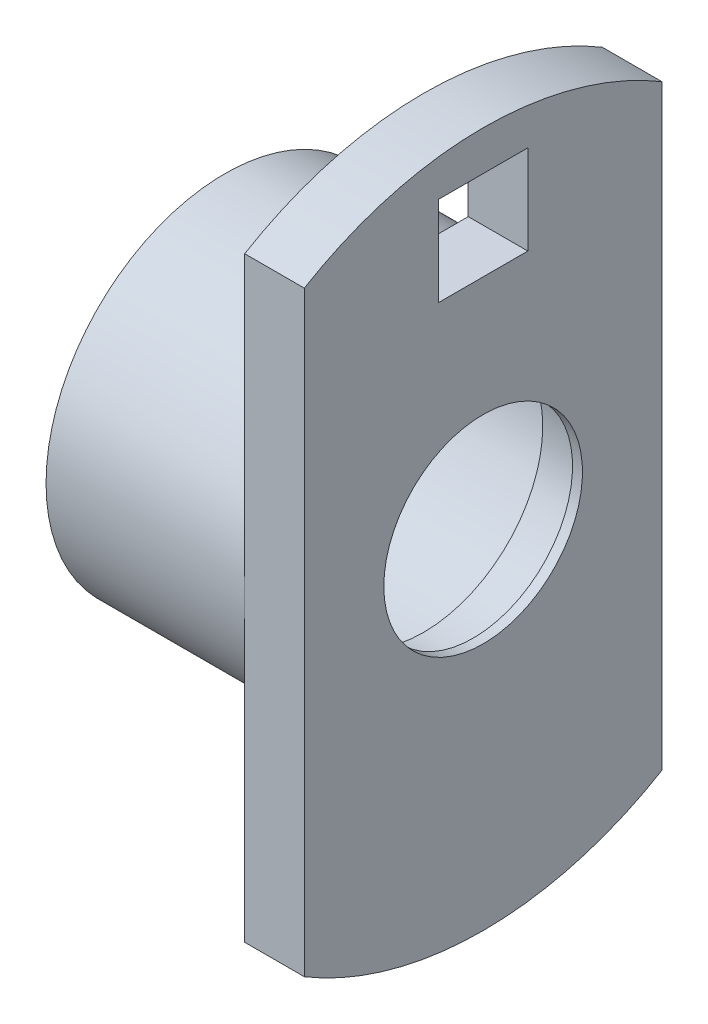
SolidWorks part; units mm, degrees
ref_plane "Front Plane" through (0, 0, 0) normal (0, 0, 1) x (1, 0, 0)
ref_plane "Top Plane" through (0, 0, 0) normal (0, 1, 0) x (1, 0, 0)
ref_plane "Right Plane" through (0, 0, 0) normal (1, 0, 0) x (0, 0, -1)
sketch "Sketch1" plane through (0, 0, 0) normal (0, 0, 1) x (1, 0, 0)
  line L0 (-42.8096, 0) -> (42.8096, 0) construction
  line L1 (-1, 12) -> (-6, 12)
  line L2 (-6, 12) -> (-6, 16)
  line L3 (-6, 16) -> (-26, 16)
  line L4 (-26, 16) -> (-26, 18)
  line L6 (0, 35) -> (0, 10)
  line L9 (0, 10) -> (-1, 10)
  line L10 (-1, 10) -> (-1, 12)
  line L11 (-26, 18) -> (-6, 18)
  line L12 (-6, 18) -> (-6, 35)
  line L13 (-6, 35) -> (0, 35)
  point P3 (0, 0)
  point P4 (0, 0)
  dimension "D1" = 2
  dimension "D2" = 6
  dimension "D3" = 5
  dimension "D4" = 24
  dimension "D5" = 32
  dimension "D6" = 2
  dimension "D7" = 70
  dimension "D8" = 6
  dimension "D9" = 20
revolve "Revolve1" add sketch "Sketch1" angle 360 about L0
sketch "Sketch2" plane through (0, 0, 0) normal (1, 0, 0) x (0, 0, -1)
  line L0 (0, 35) -> (0, 18) construction
  line L3 (0, 35) -> (0, 10) construction
  line L4 (-18, 30.0167) -> (-18, -30.0167)
  line L5 (-4.5, 22) -> (4.5, 22)
  line L6 (-4.5, 22) -> (-4.5, 31)
  line L7 (-4.5, 31) -> (4.5, 31)
  line L8 (4.5, 22) -> (4.5, 31)
  line L9 (-4.5, 22) -> (4.5, 31) construction
  line L10 (-4.5, 31) -> (4.5, 22) construction
  line L11 (18, -30.0167) -> (18, 30.0167)
  circle A0 centre (0, 0) radius 35 construction
  circle A1 centre (0, 0) radius 18 construction
  circle A3 centre (0, 0) radius 35
  point P3 (0, 26.5)
  point P5 (0, 26.5)
  dimension "D1" = 9
extrude "Cut-Extrude1" cut sketch "Sketch2" against normal up to surface (6 mm away) contours L4 A3 | L5 L8 L7 L6 | L11 A3 region at (0, 0, 24.965) region at (0, 0, -24.965) region at (0, 26.5, 0) up to face at (-6, 0, 18)
